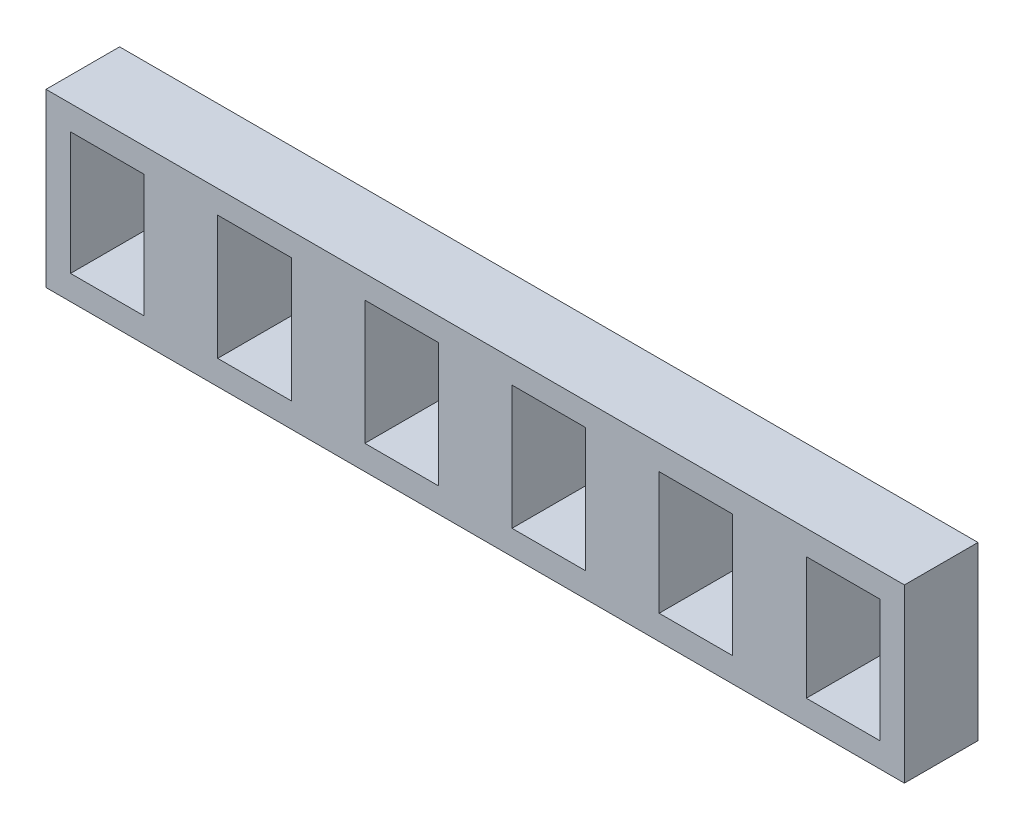
SolidWorks part; units mm, degrees
ref_plane "Alzado" through (0, 0, 0) normal (0, 0, 1) x (1, 0, 0)
ref_plane "Planta" through (0, 0, 0) normal (0, 1, 0) x (1, 0, 0)
ref_plane "Vista lateral" through (0, 0, 0) normal (1, 0, 0) x (0, 0, -1)
sketch "Croquis1" plane through (0, 0, 0) normal (0, 0, 1) x (1, 0, 0)
  line L0 (-20.8779, 14.7212) -> (14.1221, 14.7212) construction
  line L1 (-20.8779, 18.2212) -> (14.1221, 18.2212)
  line L2 (-20.8779, 18.2212) -> (-20.8779, 11.2212)
  line L3 (-20.8779, 11.2212) -> (14.1221, 11.2212)
  line L4 (14.1221, 18.2212) -> (14.1221, 11.2212)
  line L5 (-19.8779, 18.2212) -> (-19.8779, 11.2212) construction
  line L6 (-3.3779, 18.2212) -> (-3.3779, 11.2212) construction
  line L7 (13.1221, 18.2212) -> (13.1221, 11.2212) construction
  line L8 (-16.8779, 14.7207) -> (-19.8779, 14.7207) construction
  line L9 (-19.8779, 17.2207) -> (-16.8779, 17.2207)
  line L10 (-19.8779, 17.2207) -> (-19.8779, 12.2207)
  line L11 (-19.8779, 12.2207) -> (-16.8779, 12.2207)
  line L12 (-16.8779, 17.2207) -> (-16.8779, 12.2207)
  line L13 (13.1221, 12.2207) -> (10.1221, 12.2207)
  line L14 (10.1221, 17.2207) -> (10.1221, 12.2207)
  line L15 (13.1221, 17.2207) -> (10.1221, 17.2207)
  line L16 (13.1221, 17.2207) -> (13.1221, 12.2207)
  line L45 (-13.8779, 17.2787) -> (-10.8779, 17.2787)
  line L46 (-13.8779, 17.2787) -> (-13.8779, 12.2207)
  line L47 (-13.8779, 12.2207) -> (-10.8779, 12.2207)
  line L48 (-10.8779, 17.2787) -> (-10.8779, 12.2207)
  line L49 (7.1221, 17.2207) -> (4.1221, 17.2207)
  line L50 (7.1221, 17.2207) -> (7.1221, 12.2207)
  line L51 (7.1221, 12.2207) -> (4.1221, 12.2207)
  line L52 (4.1221, 17.2207) -> (4.1221, 12.2207)
  line L69 (-7.8779, 17.2787) -> (-4.8779, 17.2787)
  line L70 (-7.8779, 17.2787) -> (-7.8779, 12.2207)
  line L71 (-7.8779, 12.2207) -> (-4.8779, 12.2207)
  line L72 (-4.8779, 17.2787) -> (-4.8779, 12.2207)
  line L73 (-1.8779, 17.2787) -> (1.1221, 17.2787)
  line L74 (-1.8779, 17.2787) -> (-1.8779, 12.2207)
  line L75 (-1.8779, 12.2207) -> (1.1221, 12.2207)
  line L76 (1.1221, 17.2787) -> (1.1221, 12.2207)
  point P23 (0, 0)
  point P28 (-3.3779, 14.7212)
  dimension "D1" = 7
  dimension "D2" = 35
  dimension "D3" = 1
  dimension "D4" = 3
  dimension "D5" = 5
  dimension "D6" = 1.0005
  dimension "D11" = 3
  dimension "D12" = 3
  dimension "D15" = 3
extrude "Saliente-Extruir1" add sketch "Croquis1" along normal blind 3 contours L4 L1 L2 L3 L52 L49 L50 L51 L9 L12 L11 L10 L15 L16 L13 L14 L45 L48 L47 L46 L69 L72 L71 L70 L73 L76 L75 L74
